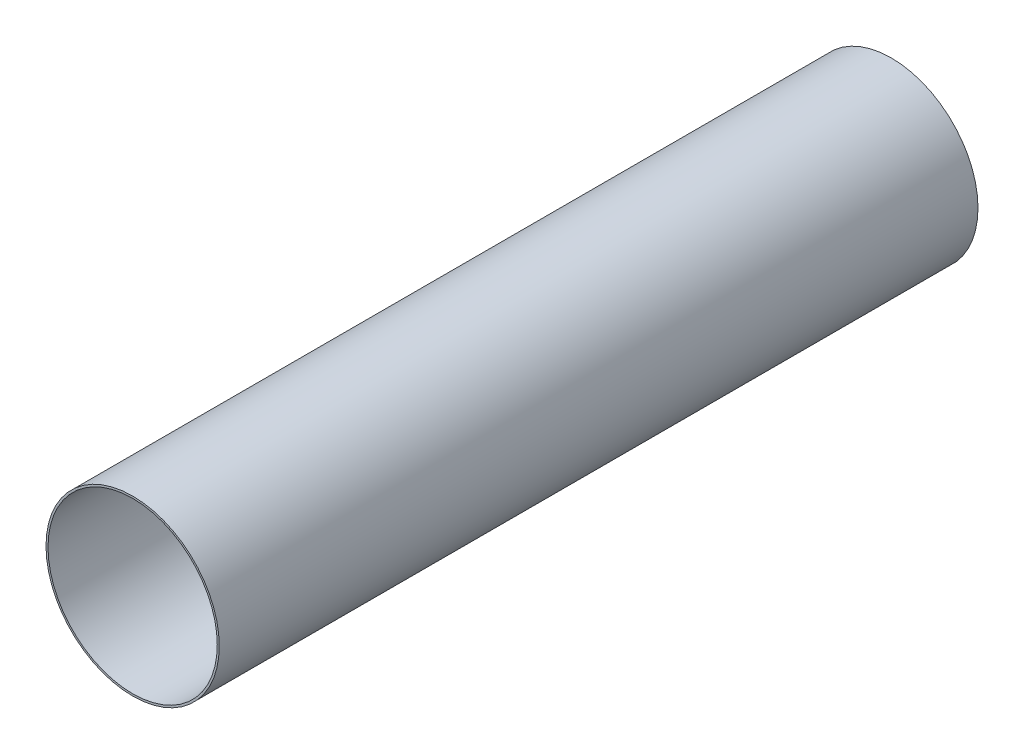
SolidWorks part; units mm, degrees
material "Thornel Mat VMA"
ref_plane "Front Plane" through (0, 0, 0) normal (0, 0, 1) x (1, 0, 0)
ref_plane "Top Plane" through (0, 0, 0) normal (0, 1, 0) x (1, 0, 0)
ref_plane "Right Plane" through (0, 0, 0) normal (1, 0, 0) x (0, 0, -1)
sketch "Sketch1" plane through (0, 0, 0) normal (0, 0, 1) x (1, 0, 0)
  circle A0 centre (0, 0) radius 86.9998
  circle A1 centre (0, 0) radius 84.9998
  dimension "D1" = 169.9997
  dimension "D2" = 173.9997
extrude "Boss-Extrude1" add sketch "Sketch1" along normal mid plane 762
